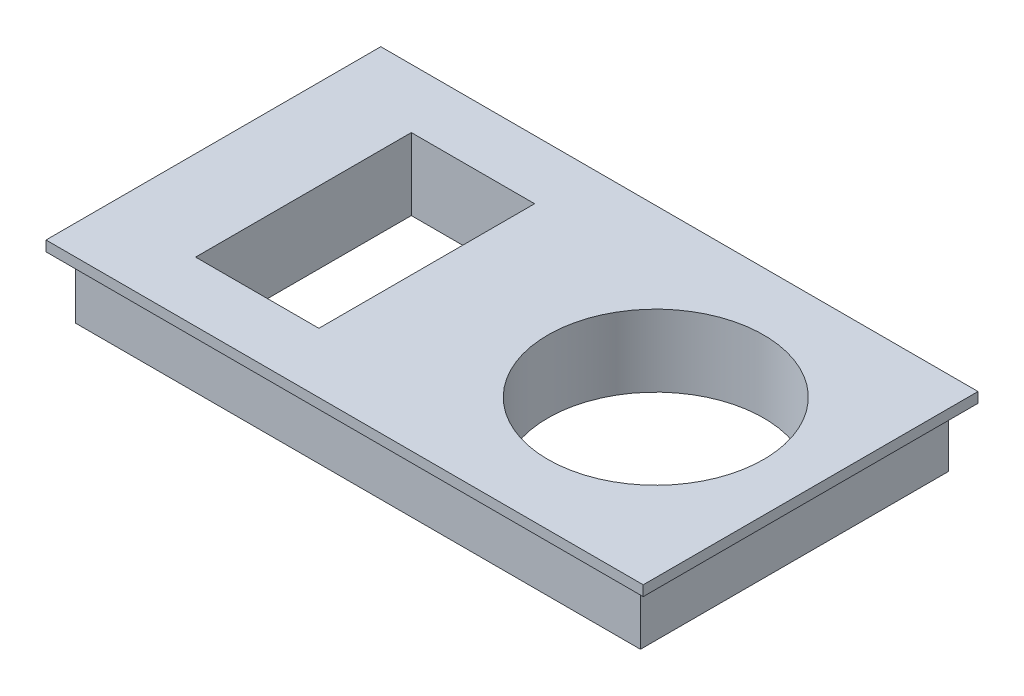
SolidWorks part; units mm, degrees
material "ABS"
ref_plane "Front Plane" through (0, 0, 0) normal (0, 0, 1) x (1, 0, 0)
ref_plane "Top Plane" through (0, 0, 0) normal (0, 1, 0) x (1, 0, 0)
ref_plane "Right Plane" through (0, 0, 0) normal (1, 0, 0) x (0, 0, -1)
sketch "Sketch1" plane through (0, 0, 0) normal (0, 1, 0) x (1, 0, 0)
  line L0 (27.5, 15) -> (-27.5, 15)
  line L1 (27.5, 15) -> (27.5, -15)
  line L2 (27.5, -15) -> (-27.5, -15)
  line L3 (-27.5, 15) -> (-27.5, -15)
  line L4 (27.5, 15) -> (-27.5, -15) construction
  line L5 (27.5, -15) -> (-27.5, 15) construction
  line L6 (-20.2127, 10.4111) -> (-8.2127, 10.4111)
  line L7 (-20.2127, 10.4111) -> (-20.2127, -10.5889)
  line L8 (-20.2127, -10.5889) -> (-8.2127, -10.5889)
  line L9 (-8.2127, 10.4111) -> (-8.2127, -10.5889)
  line L10 (-20.2127, 10.4111) -> (-8.2127, -10.5889) construction
  line L11 (-20.2127, -10.5889) -> (-8.2127, 10.4111) construction
  line L14 (29.1944, 16.1628) -> (-28.9377, 16.1628)
  line L15 (29.1944, 16.1628) -> (29.1944, -16.4246)
  line L16 (29.1944, -16.4246) -> (-28.9377, -16.4246)
  line L17 (-28.9377, 16.1628) -> (-28.9377, -16.4246)
  line L18 (29.1944, 16.1628) -> (-28.9377, -16.4246) construction
  line L19 (29.1944, -16.4246) -> (-28.9377, 16.1628) construction
  circle A0 centre (13.9934, 0) radius 10.5
  point P12 (0.1284, -0.1309)
extrude "Boss-Extrude1" add sketch "Sketch1" against normal blind 7 contours L0 L3 L2 L1 A0 L6 L9 L8 L7 region at (-1.203, 0, -0.0213)
extrude "Boss-Extrude2" add sketch "Sketch1<3>" against normal blind 1 contours L14 L17 L16 L15 L3 L0 L1 L2 region at (28.5279, 0, 0.1309)
sketch "Sketch1<3>" plane through (0, 0, 0) normal (0, 1, 0) x (1, 0, 0) same geometry as "Sketch1"
